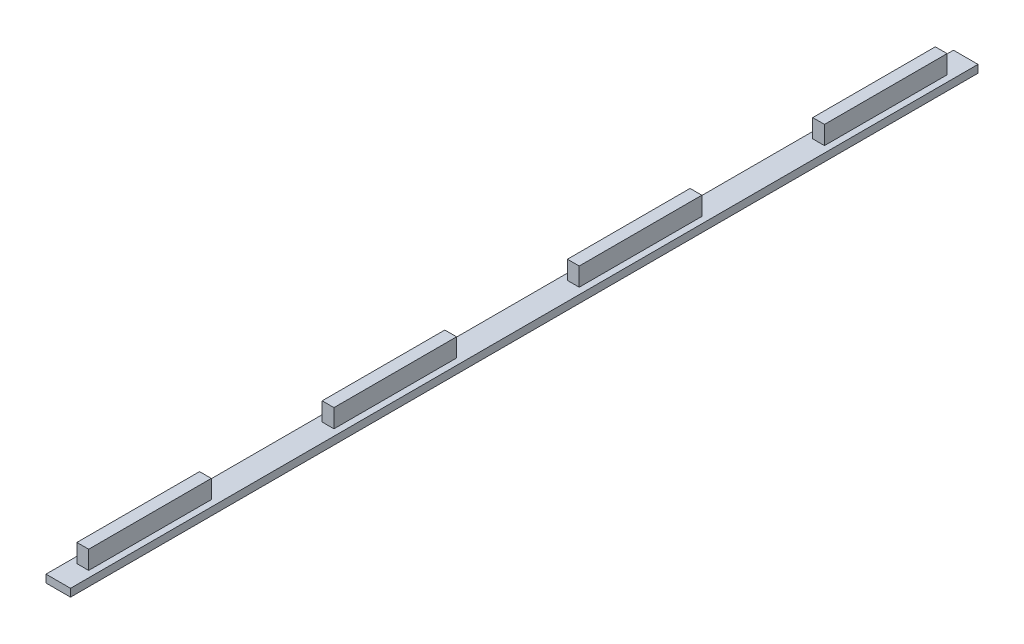
SolidWorks part; units mm, degrees
ref_plane "Front Plane" through (0, 0, 0) normal (0, 0, 1) x (1, 0, 0)
ref_plane "Top Plane" through (0, 0, 0) normal (0, 1, 0) x (1, 0, 0)
ref_plane "Right Plane" through (0, 0, 0) normal (1, 0, 0) x (0, 0, -1)
sketch "Sketch1" plane through (0, 0, 0) normal (0, 1, 0) x (1, 0, 0)
  line L0 (0, 117.475) -> (0, -117.475) construction
  line L1 (-3.175, 117.475) -> (3.175, 117.475)
  line L2 (-3.175, 117.475) -> (-3.175, -117.475)
  line L3 (-3.175, -117.475) -> (3.175, -117.475)
  line L4 (3.175, 117.475) -> (3.175, -117.475)
  line L5 (-1.524, 79.375) -> (-1.524, 47.625)
  line L6 (-1.524, 111.125) -> (1.524, 111.125)
  line L7 (-1.524, 111.125) -> (-1.524, 79.375)
  line L8 (-1.524, 79.375) -> (1.524, 79.375)
  line L9 (1.524, 111.125) -> (1.524, 79.375)
  line L10 (-1.524, 79.375) -> (1.524, 79.375)
  line L11 (1.524, 79.375) -> (1.524, 47.625)
  line L12 (-1.524, 47.625) -> (1.524, 47.625)
  line L13 (-1.524, 47.625) -> (-1.524, 15.875)
  line L14 (-1.524, 47.625) -> (1.524, 47.625)
  line L15 (1.524, 47.625) -> (1.524, 15.875)
  line L16 (-1.524, 15.875) -> (1.524, 15.875)
  line L17 (-1.524, 15.875) -> (-1.524, -15.875)
  line L18 (-1.524, 15.875) -> (1.524, 15.875)
  line L19 (1.524, 15.875) -> (1.524, -15.875)
  line L20 (-1.524, -15.875) -> (1.524, -15.875)
  line L21 (-1.524, -15.875) -> (-1.524, -47.625)
  line L22 (-1.524, -15.875) -> (1.524, -15.875)
  line L23 (1.524, -15.875) -> (1.524, -47.625)
  line L24 (-1.524, -47.625) -> (1.524, -47.625)
  line L25 (-1.524, -47.625) -> (-1.524, -79.375)
  line L26 (-1.524, -47.625) -> (1.524, -47.625)
  line L27 (1.524, -47.625) -> (1.524, -79.375)
  line L28 (-1.524, -79.375) -> (1.524, -79.375)
  line L29 (-1.524, -79.375) -> (-1.524, -111.125)
  line L30 (-1.524, -79.375) -> (1.524, -79.375)
  line L31 (1.524, -79.375) -> (1.524, -111.125)
  line L32 (-1.524, -111.125) -> (1.524, -111.125)
  point P4 (-3.175, 0)
  point P8 (0, 0)
  point P13 (0, 111.125)
  point P14 (-1.524, 69.5788)
  point P15 (-1.524, 76.5384)
  point P40 (-1.524, 71.3131)
  dimension "D1" = 234.95
  dimension "D2" = 6.35
  dimension "D3" = 3.048
  dimension "D4" = 31.75
  dimension "D6" = 6.35
  dimension "D5" = 7
extrude "Boss-Extrude1" add sketch "Sketch1" along normal blind 2 contours L1 L0 L6 L9 L11 L15 L19 L23 L27 L31 L32 L3 L4 | L0 L1 L2 L3 L32 L29 L25 L21 L17 L13 L5 L7 L6 | L0 L6 L7 L8 | L6 L0 L10 L9 | L10 L0 L14 L11 | L0 L8 L5 L12 | L0 L12 L13 L16 | L14 L0 L18 L15 | L18 L0 L22 L19 | L0 L16 L17 L20 | L26 L0 L30 L27 | L0 L24 L25 L28 | L0 L28 L29 L32 | L30 L0 L32 L31 | L22 L0 L26 L23 | L0 L20 L21 L24 region at (2.2741, 0, 0) region at (-2.2741, 0, 0) region at (0.762, 0, -95.25) region at (-0.762, 0, -95.25) region at (0.762, 0, -63.5) region at (-0.762, 0, -63.5) region at (0.762, 0, -31.75) region at (-0.762, 0, -31.75) region at (0.762, 0, 0) region at (-0.762, 0, 0) region at (-0.762, 0, 95.25) region at (0.762, 0, 95.25) region at (0.762, 0, 31.75) region at (-0.762, 0, 31.75) region at (-0.762, 0, 63.5) region at (0.762, 0, 63.5)
extrude "Boss-Extrude2" add sketch "Sketch1<3>" along normal blind 4.7625 from surface contours L6 L0 L10 L9 | L0 L6 L7 L8 | L14 L0 L18 L15 | L0 L12 L13 L16 | L22 L0 L26 L23 | L0 L20 L21 L24 | L30 L0 L32 L31 | L0 L28 L29 L32 region at (0.762, 0, -95.25) region at (-0.762, 0, -95.25) region at (0.762, 0, -31.75) region at (-0.762, 0, -31.75) region at (-0.762, 0, 95.25) region at (0.762, 0, 95.25) region at (0.762, 0, 31.75) region at (-0.762, 0, 31.75) starting at face at (0, 2, 0)
sketch "Sketch1<3>" plane through (0, 0, 0) normal (0, 1, 0) x (1, 0, 0) same geometry as "Sketch1"
